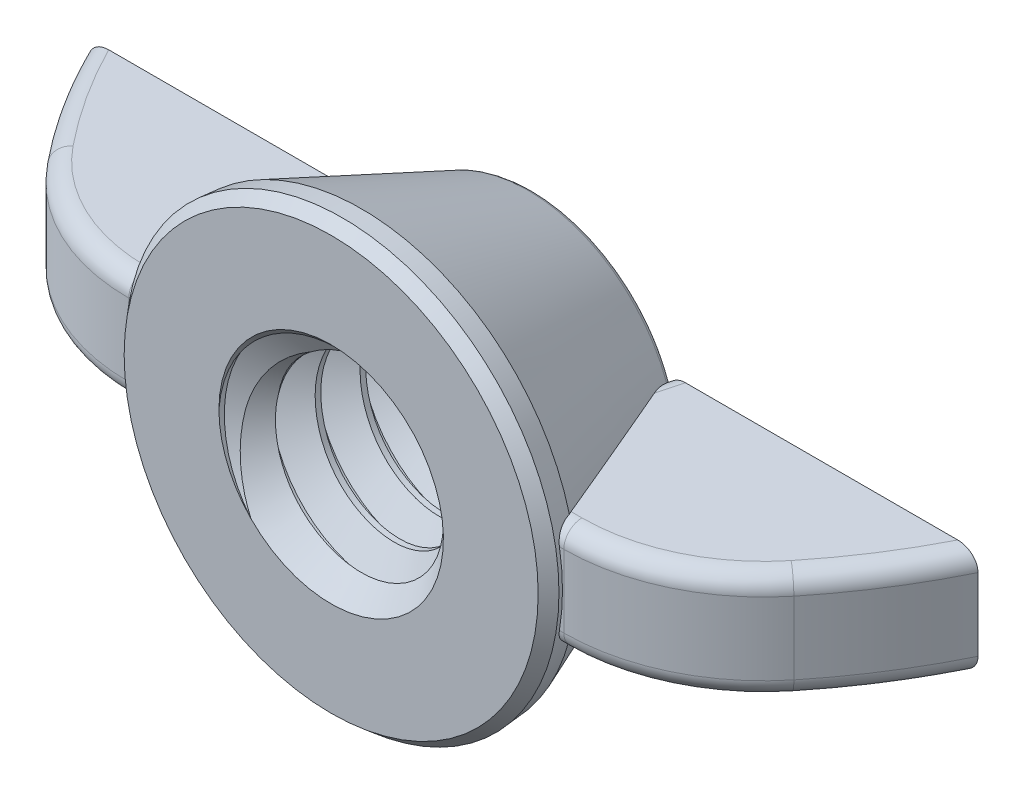
SolidWorks part; units mm, degrees
ref_plane "Front Plane" through (0, 0, 0) normal (0, 0, 1) x (1, 0, 0)
ref_plane "Top Plane" through (0, 0, 0) normal (0, 1, 0) x (1, 0, 0)
ref_plane "Right Plane" through (0, 0, 0) normal (1, 0, 0) x (0, 0, -1)
sketch "Sketch1" plane through (0, 0, 0) normal (0, 0, 1) x (1, 0, 0)
  circle A0 centre (0, 0) radius 3.175
  circle A1 centre (0, 0) radius 6.1516
  dimension "D1" = 12.3031
sketch "Sketch2" plane through (0, 0, 0) normal (0, 1, 0) x (1, 0, 0)
  line L0 (0, 0) -> (0, 15.875) construction
  line L1 (-3.175, 0) -> (3.175, 0) construction
  line L2 (-14.2875, 15.875) -> (14.2875, 15.875) construction
  line L3 (14.2875, 15.875) -> (14.2875, 0) construction
  line L4 (-14.2875, 15.875) -> (-14.2875, 0) construction
  line L5 (-14.2875, 0) -> (14.2875, 0) construction
  line L6 (-4.1928, 5.715) -> (4.1928, 5.715) construction
  line L7 (0, 0) -> (0, 5.715) construction
  line L8 (-4.3144, 0.8572) -> (6.1516, 0.8572) construction
  line L9 (6.1516, 0) -> (6.1516, 5.715) construction
  line L10 (3.7735, 5.715) -> (6.5552, 16.0963)
  line L12 (4.1928, 5.715) -> (4.1928, 0.4286) construction
  line L13 (-6.1516, 0) -> (6.1516, 0) construction
  line L14 (6.1516, 0.8572) -> (4.1928, 5.715) construction
  line L15 (6.5552, 16.0963) -> (14.6189, 13.631)
  line L16 (14.6189, 13.631) -> (8.5296, 0.4286)
  line L17 (6.1516, 0.4286) -> (8.5296, 0.4286)
  line L19 (3.7735, 0.4286) -> (6.1516, 0.4286)
  line L20 (-3.7735, 5.715) -> (3.7735, 5.715) construction
  line L21 (3.7735, 5.715) -> (3.7735, 0.4286)
  circle A3 centre (13.4331, 13.1001) radius 0.8544 construction
  circle A4 centre (7.1515, 15.0206) radius 0.8544 construction
  dimension "D6" = 1.7088
  dimension "D2" = 5.715
  dimension "D4" = 8.3857
  dimension "D1" = 0.8572
  dimension "D3" = 21.96
  dimension "D5" = 0.4286
  dimension "D8" = 17
  dimension "D9" = 7.5471
  dimension "D7" = 15
sketch "Sketch13" plane through (0, 0, 0) normal (0, 1, 0) x (1, 0, 0)
  line L1 (3.7735, 5.715) -> (3.7735, 0.4286) construction
  line L2 (3.7735, 5.715) -> (6.5552, 16.0963) construction
  line L3 (-14.2875, 15.875) -> (14.2875, 15.875) construction
  line L4 (14.2875, 15.875) -> (14.2875, 0) construction
  line L5 (6.1516, 0.4286) -> (8.5296, 0.4286) construction
  line L6 (3.7735, 0.4286) -> (6.1516, 0.4286) construction
  line L7 (0, 0) -> (0, 5.715) construction
  line L8 (-3.175, 0) -> (3.175, 0) construction
  line L9 (0, 0) -> (0, 15.875) construction
  line L10 (-4.1928, 5.715) -> (4.1928, 5.715) construction
  line L11 (3.7735, 0.4286) -> (6.1516, 0.4286)
  line L12 (3.7735, 5.715) -> (3.7735, 0.4286)
  line L13 (3.7735, 5.715) -> (6.3262, 15.2417)
  circle A0 centre (13.4331, 13.1001) radius 0.8544 construction
  circle A1 centre (7.1515, 15.0206) radius 0.8544 construction
  arc A5 (14.2875, 13.1001) -> (13.9109, 13.8084) centre (13.4331, 13.1001) ccw
  arc A6 (7.1515, 15.875) -> (6.3262, 15.2417) centre (7.1515, 15.0206) ccw
  arc A7 (10.5535, 2.5321) -> (14.2875, 13.1001) centre (-2.5346, 13.1001) ccw
  arc A8 (13.9109, 13.8084) -> (7.1515, 15.875) centre (7.1515, 3.7873) ccw
  arc A10 (6.1516, 0.4286) -> (10.5535, 2.5321) centre (6.1516, 6.0864) ccw
extrude "Extrude2" add sketch "Sketch13" along normal mid plane 3.0758
sketch "Sketch3" plane through (0, 0, 0) normal (0, 0, 1) x (1, 0, 0)
  circle A0 centre (0, 0) radius 6.1516 construction
  circle A1 centre (0, 0) radius 6.1516
extrude "Extrude1" add sketch "Sketch3" against normal up to vertex (0.8572 mm away) draft 5 separate body up to point (6.1516, 0, -0.8572)
sketch "Sketch15" plane through (0, 0, -0.8572) normal (0, 0, -1) x (-1, 0, 0)
  circle A1 centre (0, 0) radius 6.0766
  circle A2 centre (0, 0) radius 6.0766
  dimension "D1" = 0
extrude "Extrude3" add sketch "Sketch15" along normal up to vertex (4.8578 mm away) draft 21.96 up to point (0, 0, -5.715)
fillet "Fillet3" radius 0.254 1 edges at (-4.1178, 0, -5.715)
sketch "Sketch12" plane through (0, 0, -5.715) normal (0, 0, -1) x (-1, 0, 0)
  circle A1 centre (0, 0) radius 6.0766
  circle A2 centre (0, 0) radius 6.0766 construction
  dimension "D1" = 12.1531
sketch "Sketch4" plane through (0, 0, 0) normal (0, 0, 1) x (1, 0, 0)
  circle A0 centre (0, 0) radius 3.175 construction
  circle A1 centre (0, 0) radius 3.175
extrude "Cut-Extrude1" cut sketch "Sketch4" against normal through all
sketch "Sketch5" plane through (0, 0, 0) normal (0, 0, 1) x (1, 0, 0)
  circle A0 centre (0, 0) radius 3.175 construction
  circle A1 centre (0, 0) radius 3.175
curve "Helix/Spiral1" pitch 1.27 height 8.89 turns 7 parameters "pitch"=1.27
sketch "Sketch6" plane through (0, 0, 0) normal (0, 1, 0) x (1, 0, 0)
  line L0 (-3.175, -1.1112) -> (-2.3501, -0.635)
  line L1 (-2.3501, -0.635) -> (-2.3501, -0.4762)
  line L2 (-2.3501, -0.4762) -> (-3.175, 0)
  line L3 (-3.175, -1.1112) -> (-3.175, 0)
  line L4 (-3.175, -0.5556) -> (-2.3501, -0.5556) construction
  line L5 (-2.7626, -0.8731) -> (-2.7626, -0.2381) construction
  line L6 (-3.175, 0) -> (3.175, 0) construction
  dimension "D1" = 60
  dimension "D2" = 0.1588
  dimension "D3" = 0.635
sweep "Sweep1" add profiles "Sketch6" path "Helix/Spiral1"
sketch "Sketch7" plane through (0, 0, 0) normal (0, 0, 1) x (1, 0, 0)
  circle A1 centre (0, 0) radius 6.1516
  circle A2 centre (0, 0) radius 6.1516
  dimension "D1" = 0
extrude "Cut-Extrude2" cut sketch "Sketch7" along normal through all
ref_plane "Plane1" through (0, 0, -5.715) normal (0, 0, 1) x (1, 0, 0)
sketch "Sketch8" plane through (0, 0, -5.715) normal (0, 0, 1) x (1, 0, 0)
  circle A0 centre (0, 0) radius 6.0766 construction
  circle A2 centre (0, 0) radius 6.0766
extrude "Cut-Extrude3" cut sketch "Sketch8" against normal through all
sketch "Sketch9" plane through (0, 0, 0) normal (0, 0, 1) x (1, 0, 0)
  circle A1 centre (0, 0) radius 3.175
  circle A2 centre (0, 0) radius 3.175
  dimension "D1" = 0
extrude "Cut-Extrude4" cut sketch "Sketch9" against normal through all draft 45
sketch "Sketch11" plane through (0, 0, -5.715) normal (0, 0, 1) x (1, 0, 0)
  circle A0 centre (0, 0) radius 3.175 construction
  circle A1 centre (0, 0) radius 3.1242
  circle A2 centre (0, 0) radius 3.175 construction
  dimension "D1" = 0.0508
extrude "Cut-Extrude5" cut sketch "Sketch11" along normal through all draft 45
chamfer "Chamfer1" distance 0.3215 angle 45 1 edges at (6.1516, 0, 0)
fillet "Fillet4" radius 0.5126 14 edges at (4.9626, 1.5379, -0.4286) (8.5909, 1.5379, -0.9815) (6.6314, 1.5379, -15.6984) (10.6856, 1.5379, -15.3468) (14.1875, 1.5379, -13.5012) (4.9626, -1.5379, -0.4286) (8.5909, -1.5379, -0.9815) (6.6314, -1.5379, -15.6984) (10.6856, -1.5379, -15.3468) (14.1875, -1.5379, -13.5012) (13.3266, 1.5379, -7.496) (13.3266, -1.5379, -7.496) (5.0499, 1.5379, -10.4784) (5.0499, -1.5379, -10.4784)
mirror "Mirror6" about plane through (0, 0, 0) normal (1, 0, 0) of bodies 108 113
combine bodies "Combine2" operation type add bodies to combine 116 108 107
sketch "Sketch16" plane through (0, 0, -5.715) normal (0, 0, -1) x (-1, 0, 0)
  circle A0 centre (0, 0) radius 15.3226
extrude "Cut-Extrude6" cut sketch "Sketch16" along normal through all
equation "\"D1@Sketch1\" = \"thread dia@Sketch1\"*1.725"
equation "\"D2@Sketch2\" = \"B@Sketch2\"*.36"
equation "\"D3@Helix/Spiral1\" = \"D2@Sketch2\"+.125"
equation "\"D2@Sketch6\" = \"pitch@Helix/Spiral1\"*.125"
equation "\"D3@Sketch6\" = \"pitch@Helix/Spiral1\"*.5"
equation "\"D4@Sketch2\" = \"D1@Sketch12\"*.69"
equation "\"D1@Extrude2\" = \"D1@Sketch1\"*.25"
equation "\"D1@Sketch2\" = \"D2@Sketch2\"*.150"
equation "\"D5@Sketch2\" = \"D1@Sketch2\"/2"
equation "\"D3@Extrude3\" = \"D3@Sketch2\""
equation "\"D1@Chamfer1\" = \"D5@Sketch2\"*.75"
equation "\"D9@Sketch2\" = \"D4@Sketch2\"*.9"
equation "\"D6@Sketch2\" = \"D1@Extrude2\"/1.8"
equation "\"D1@Fillet4\" = \"D1@Extrude2\"/6"
